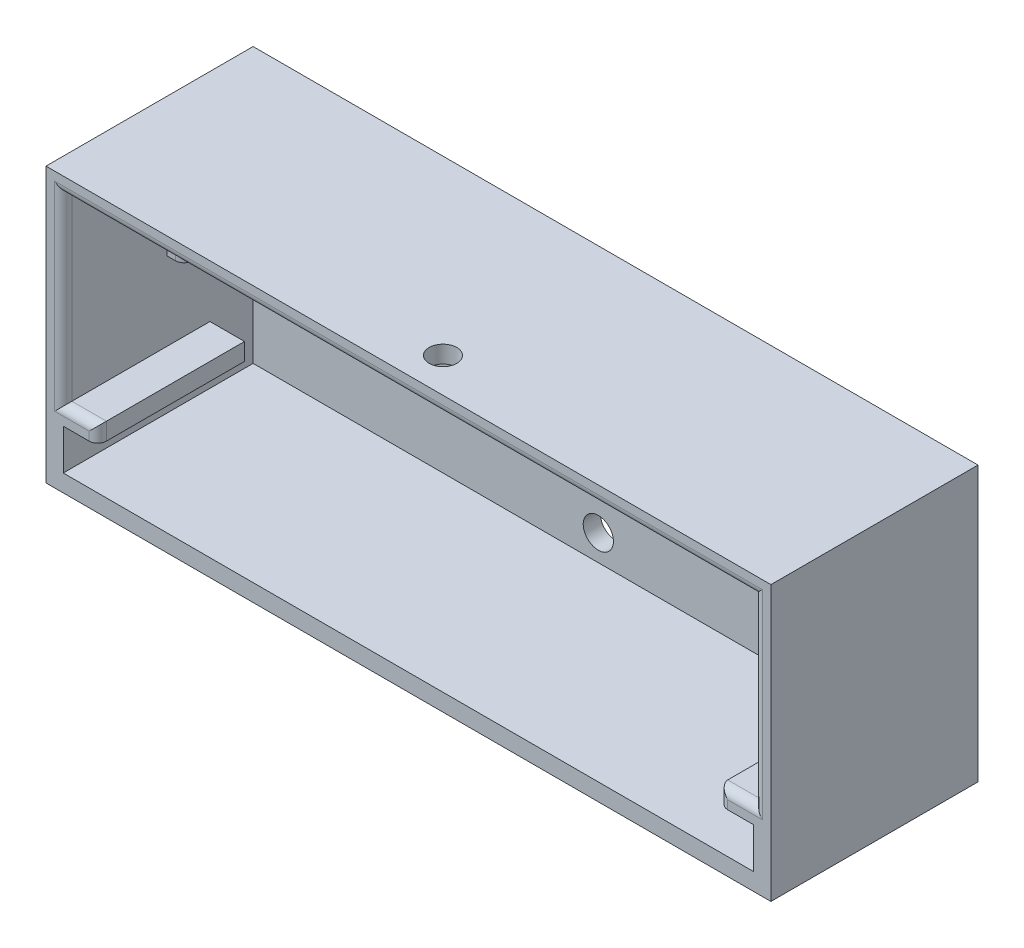
SolidWorks part; units mm, degrees
ref_plane "Front Plane" through (0, 0, 0) normal (0, 0, 1) x (1, 0, 0)
ref_plane "Top Plane" through (0, 0, 0) normal (0, 1, 0) x (1, 0, 0)
ref_plane "Right Plane" through (0, 0, 0) normal (1, 0, 0) x (0, 0, -1)
sketch "Sketch1" plane through (0, 0, 0) normal (0, 0, 1) x (1, 0, 0)
  line L1 (42, -15.9) -> (-42, -15.9)
  line L2 (42, -15.9) -> (42, 15.9)
  line L3 (42, 15.9) -> (-42, 15.9)
  line L4 (-42, -15.9) -> (-42, 15.9)
  line L5 (42, -15.9) -> (-42, 15.9) construction
  line L6 (42, 15.9) -> (-42, -15.9) construction
  point P0 (0, 0)
  dimension "D1" = 31.8
  dimension "D2" = 84
extrude "Boss-Extrude1" add sketch "Sketch1" along normal blind 2
sketch "Sketch2" plane through (0, 0, 2) normal (0, 0, 1) x (1, 0, 0)
  line L1 (42, -15.9) -> (-42, -15.9)
  line L2 (42, -15.9) -> (42, 15.9)
  line L3 (42, 15.9) -> (-42, 15.9)
  line L4 (-42, -15.9) -> (-42, 15.9)
  line L5 (42, -15.9) -> (-42, 15.9) construction
  line L6 (42, 15.9) -> (-42, -15.9) construction
  line L7 (40, -13.9) -> (-40, -13.9)
  line L8 (40, -13.9) -> (40, 13.9)
  line L9 (40, 13.9) -> (-40, 13.9)
  line L10 (-40, -13.9) -> (-40, 13.9)
  line L11 (40, -13.9) -> (-40, 13.9) construction
  line L12 (40, 13.9) -> (-40, -13.9) construction
  point P0 (0, 0)
  point P7 (0, 0)
  dimension "D1" = 2
  dimension "D2" = 2
extrude "Boss-Extrude2" add sketch "Sketch2" along normal blind 22
sketch "Sketch3" plane through (0, 0, 2) normal (0, 0, 1) x (1, 0, 0)
  line L0 (-40, 13.9) -> (-40, -13.9) construction
  line L1 (-40, -7.2) -> (-36, -7.2)
  line L2 (-40, -7.2) -> (-40, -9.2)
  line L3 (-40, -9.2) -> (-36, -9.2)
  line L4 (-36, -7.2) -> (-36, -9.2)
  line L5 (40, -13.9) -> (40, 13.9) construction
  line L6 (40, -7.2) -> (36, -7.2)
  line L7 (40, -7.2) -> (40, -9.2)
  line L8 (40, -9.2) -> (36, -9.2)
  line L9 (36, -7.2) -> (36, -9.2)
  line L10 (40, 13.9) -> (-40, 13.9) construction
  line L11 (40, 13.9) -> (-40, 13.9) construction
  dimension "D1" = 2
  dimension "D2" = 2
  dimension "D3" = 4
  dimension "D4" = 4
  dimension "D5" = 21.1
  dimension "D6" = 21.1
extrude "Boss-Extrude3" add sketch "Sketch3" along normal up to surface (22 mm away) from offset 5 up to face at (0, 0, 24)
sketch "Sketch11" plane through (0, 15.9, 0) normal (0, 1, 0) x (1, 0, 0)
  line L0 (42, -24) -> (-42, -24) construction
  line L1 (-42, -24) -> (-42, 0) construction
  circle A0 centre (0, -20) radius 1.6
  dimension "D1" = 4
  dimension "D2" = 42
  dimension "D3" = 3.2
extrude "Cut-Extrude5" cut sketch "Sketch11" against normal up to surface (2 mm away) contours A0 up to face at (0, 13.9, 13)
sketch "Sketch13" plane through (0, 0, 0) normal (0, 0, -1) x (-1, 0, 0)
  line L0 (42, -15.9) -> (-42, -15.9) construction
  line L1 (-40, -7.9) -> (-31, -7.9)
  line L2 (-40, -7.9) -> (-40, -13.9)
  line L3 (-40, -13.9) -> (-31, -13.9)
  line L4 (-31, -7.9) -> (-31, -13.9)
  line L5 (-42, -15.9) -> (-42, 15.9) construction
  line L6 (-42, 15.9) -> (42, 15.9) construction
  line L7 (42, 15.9) -> (42, -15.9) construction
  circle A0 centre (0, 3.4) radius 1.75
  circle A1 centre (0, -10.9) radius 1.75
  dimension "D5" = 12.5
  dimension "D6" = 3.5
  dimension "D7" = 5
  dimension "D8" = 42
  dimension "D9" = 42
  dimension "D1" = 6
  dimension "D2" = 9
  dimension "D3" = 2
  dimension "D4" = 2
extrude "Cut-Extrude6" cut sketch "Sketch13" against normal up to surface (2 mm away) up to face at (0, 0, 2)
chamfer "Chamfer1" distance 5 angle 45 1 edges at (36, -8.2, 7)
sketch "Sketch14" plane through (0, 0, 2) normal (0, 0, 1) x (1, 0, 0)
  line L0 (-40, 13.9) -> (-40, -7.2) construction
  line L1 (-40, 3.9) -> (-38, 3.9)
  line L2 (-40, 3.9) -> (-40, 1.9)
  line L3 (-40, 1.9) -> (-38, 1.9)
  line L4 (-38, 3.9) -> (-38, 1.9)
  line L5 (40, -7.2) -> (40, 13.9) construction
  line L6 (40, 3.9) -> (38, 3.9)
  line L7 (40, 3.9) -> (40, 1.9)
  line L8 (40, 1.9) -> (38, 1.9)
  line L9 (38, 3.9) -> (38, 1.9)
  line L10 (40, 13.9) -> (-40, 13.9) construction
  line L11 (40, 13.9) -> (-40, 13.9) construction
  dimension "D1" = 2
  dimension "D2" = 2
  dimension "D3" = 2
  dimension "D4" = 2
  dimension "D5" = 10
  dimension "D6" = 10
extrude "Boss-Extrude4" add sketch "Sketch14" along normal blind 10
fillet "Fillet1" radius 1 9 edges at (-36, -8.2, 24) (-38, -7.2, 24) (-40, 3.35, 24) (0, 13.9, 24) (38, 2.9, 12) (38, -7.2, 24) (40, 3.35, 24) (36, -8.2, 24) (-38, 2.9, 12)
